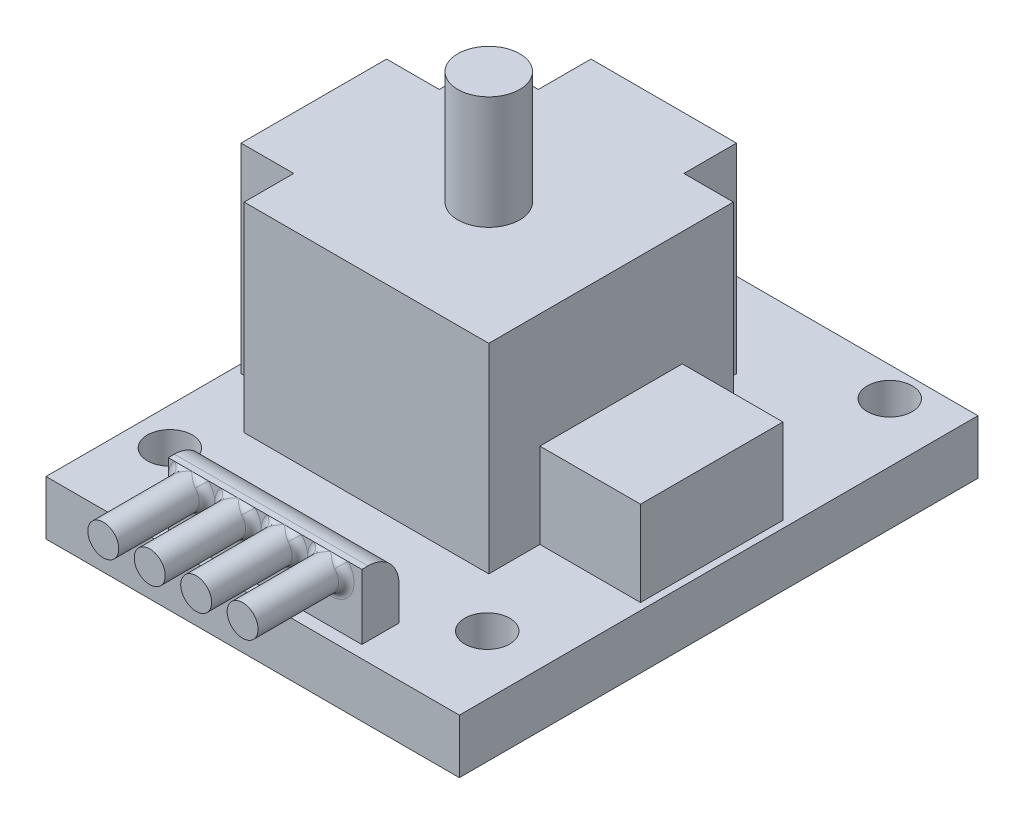
SolidWorks part; units mm, degrees
ref_plane "Спереди" through (0, 0, 0) normal (0, 0, 1) x (1, 0, 0)
ref_plane "Сверху" through (0, 0, 0) normal (0, 1, 0) x (1, 0, 0)
ref_plane "Справа" through (0, 0, 0) normal (1, 0, 0) x (0, 0, -1)
sketch "Sketch1" plane through (0, 0, 0) normal (0, 1, 0) x (1, 0, 0)
  line L1 (13.35, -16.75) -> (-13.35, -16.75)
  line L2 (13.35, -16.75) -> (13.35, 16.75)
  line L3 (13.35, 16.75) -> (-13.35, 16.75)
  line L4 (-13.35, -16.75) -> (-13.35, 16.75)
  line L5 (13.35, -16.75) -> (-13.35, 16.75) construction
  line L6 (13.35, 16.75) -> (-13.35, -16.75) construction
  point P0 (0, 0)
  dimension "D1" = 26.7
  dimension "D2" = 33.5
extrude "Boss-Extrude1" add sketch "Sketch1" along normal blind 3.5
sketch "Sketch2" plane through (0, 3.5, 0) normal (0, 1, 0) x (1, 0, 0)
  line L0 (13.35, 0) -> (-13.35, 0) construction
  line L1 (6.4, -7.9) -> (-9.4, -7.9)
  line L2 (6.4, -7.9) -> (6.4, 7.9)
  line L3 (6.4, 7.9) -> (-9.4, 7.9)
  line L4 (-9.4, -7.9) -> (-9.4, 7.9)
  line L5 (6.4, -7.9) -> (-9.4, 7.9) construction
  line L6 (6.4, 7.9) -> (-9.4, -7.9) construction
  line L7 (13.35, -16.75) -> (13.35, 16.75) construction
  line L8 (-13.35, 16.75) -> (-13.35, -16.75) construction
  point P0 (-1.5, 0)
  dimension "D1" = 15.8
  dimension "D2" = 1.5
extrude "Boss-Extrude2" add sketch "Sketch2" along normal blind 12.9
sketch "Sketch3" plane through (0, 16.4, 0) normal (0, 1, 0) x (1, 0, 0)
  circle A0 centre (0, 0) radius 1.9
  dimension "D1" = 3.8
extrude "Boss-Extrude3" add sketch "Sketch3" along normal blind 6.9
sketch "Sketch4" plane through (-9.4, 0, 0) normal (-1, 0, 0) x (0, 0, 1)
  line L0 (0, 16.4) -> (0, 3.5) construction
  line L1 (-7.9, 16.4) -> (7.9, 16.4) construction
  line L2 (-7.9, 3.5) -> (7.9, 3.5) construction
  line L4 (4.7, 3.5) -> (-4.7, 3.5)
  line L5 (4.7, 3.5) -> (4.7, 16.4)
  line L6 (4.7, 16.4) -> (-4.7, 16.4)
  line L7 (-4.7, 3.5) -> (-4.7, 16.4)
  line L8 (4.7, 3.5) -> (-4.7, 16.4) construction
  line L9 (4.7, 16.4) -> (-4.7, 3.5) construction
  point P6 (0, 9.95)
  dimension "D1" = 9.4
extrude "Boss-Extrude4" add sketch "Sketch4" along normal blind 3.4
sketch "Sketch5" plane through (0, 0, -7.9) normal (0, 0, -1) x (-1, 0, 0)
  line L0 (1.5, 16.4) -> (1.5, 3.5) construction
  line L1 (-6.4, 16.4) -> (9.4, 16.4) construction
  line L2 (-6.4, 3.5) -> (9.4, 3.5) construction
  line L4 (-3.2, 3.5) -> (6.2, 3.5)
  line L5 (-3.2, 3.5) -> (-3.2, 16.4)
  line L6 (-3.2, 16.4) -> (6.2, 16.4)
  line L7 (6.2, 3.5) -> (6.2, 16.4)
  line L8 (-3.2, 3.5) -> (6.2, 16.4) construction
  line L9 (-3.2, 16.4) -> (6.2, 3.5) construction
  point P6 (1.5, 9.95)
  dimension "D1" = 9.4
extrude "Boss-Extrude5" add sketch "Sketch5" along normal blind 3.4
sketch "Sketch6" plane through (6.4, 0, 0) normal (1, 0, 0) x (0, 0, -1)
  line L0 (0, 16.4) -> (0, 3.5) construction
  line L1 (-7.9, 16.4) -> (7.9, 16.4) construction
  line L2 (-7.9, 3.5) -> (7.9, 3.5) construction
  line L4 (-4.6, 9) -> (4.6, 9)
  line L5 (-4.6, 9) -> (-4.6, 3.5)
  line L6 (-4.6, 3.5) -> (4.6, 3.5)
  line L7 (4.6, 9) -> (4.6, 3.5)
  line L8 (-4.6, 9) -> (4.6, 3.5) construction
  line L9 (-4.6, 3.5) -> (4.6, 9) construction
  point P6 (0, 6.25)
  dimension "D1" = 9.2
  dimension "D2" = 5.5
extrude "Boss-Extrude6" add sketch "Sketch6" along normal blind 6.5
sketch "Sketch8" plane through (0, 16.4, 0) normal (0, 1, 0) x (1, 0, 0)
  line L0 (6.4, 7.9) -> (-9.4, -7.9) construction
  circle A0 centre (-1.5, 0) radius 12.75
  point P8 (-1.5, 0)
  dimension "D1" = 25.5
extrude "Boss-Extrude7" add sketch "Sketch8" along normal blind 8
fillet "Fillet1" radius 8 1 edges at (-1.5, 24.4, 12.75)
sketch "Sketch9" plane through (0, 24.4, 0) normal (0, 1, 0) x (1, 0, 0)
  circle A0 centre (-1.5, 0) radius 4.75
extrude "Boss-Extrude8" add sketch "Sketch9" along normal blind 5.5
sketch "Sketch10" plane through (0, 29.9, 0) normal (0, 1, 0) x (1, 0, 0)
  circle A0 centre (-1.5, 0) radius 10
  dimension "D1" = 20
extrude "Boss-Extrude9" add sketch "Sketch10" along normal blind 4.4
fillet "Fillet2" radius 4 1 edges at (-1.5, 34.3, 10)
sketch "Sketch11" plane through (0, 3.5, 0) normal (0, 1, 0) x (1, 0, 0)
  line L0 (-13.35, -14.75) -> (13.35, -14.75) construction
  line L1 (-13.35, 16.75) -> (-13.35, -16.75) construction
  line L2 (13.35, -16.75) -> (13.35, 16.75) construction
  line L3 (-13.35, -16.75) -> (13.35, -16.75) construction
  line L5 (6.25, -15.95) -> (-6.25, -15.95)
  line L6 (6.25, -15.95) -> (6.25, -13.55)
  line L7 (6.25, -13.55) -> (-6.25, -13.55)
  line L8 (-6.25, -15.95) -> (-6.25, -13.55)
  line L9 (6.25, -15.95) -> (-6.25, -13.55) construction
  line L10 (6.25, -13.55) -> (-6.25, -15.95) construction
  point P8 (0, -14.75)
  dimension "D1" = 2
  dimension "D2" = 2.4
  dimension "D3" = 12.5
extrude "Boss-Extrude10" add sketch "Sketch11" along normal blind 4.2
sketch "Sketch12" plane through (0, 0, 15.95) normal (0, 0, 1) x (1, 0, 0)
  line L0 (-6.25, 6.7) -> (6.25, 6.7) construction
  line L1 (-6.25, 7.7) -> (-6.25, 3.5) construction
  line L2 (6.25, 7.7) -> (6.25, 3.5) construction
  circle A0 centre (-4.75, 6.7) radius 1
  circle A1 centre (-1.75, 6.7) radius 1
  circle A2 centre (1.25, 6.7) radius 1
  circle A3 centre (4.25, 6.7) radius 1
  dimension "D1" = 1
  dimension "D2" = 3
  dimension "D3" = 3
  dimension "D4" = 3
  dimension "D5" = 1.5
extrude "Boss-Extrude11" add sketch "Sketch12" along normal blind 5.7
fillet "Fillet3" radius 2 1 edges at (0, 7.7, 13.55)
fillet "Fillet4" radius 0.5 4 edges at (5.25, 6.7, 15.95) (2.25, 6.7, 15.95) (-0.75, 6.7, 15.95) (-3.75, 6.7, 15.95)
sketch "Sketch13" plane through (0, 0, 0) normal (0, -1, 0) x (1, 0, 0)
  line L0 (9.55, -14.85) -> (-10.95, -14.85) construction
  line L1 (-10.95, -14.85) -> (-10.95, 11.15) construction
  line L2 (-10.95, 11.15) -> (9.55, 11.15) construction
  line L3 (9.55, 11.15) -> (9.55, -14.85) construction
  line L4 (13.35, -16.75) -> (-13.35, -16.75) construction
  line L5 (-13.35, -16.75) -> (-13.35, 16.75) construction
  circle A0 centre (9.55, -14.85) radius 1.45
  circle A1 centre (-10.95, -14.85) radius 1.45
  circle A2 centre (-10.95, 11.15) radius 1.45
  circle A3 centre (9.55, 11.15) radius 1.45
  dimension "D1" = 2.9
  dimension "D2" = 20.5
  dimension "D3" = 26
  dimension "D4" = 1.9
  dimension "D5" = 2.4
extrude "Cut-Extrude1" cut sketch "Sketch13" against normal up to next
sketch "Sketch14" plane through (0, 34.3, 0) normal (0, 1, 0) x (1, 0, 0)
  line L0 (-1.5, 6) -> (-1.5, -6) construction
  circle A0 centre (-1.5, 0) radius 6 construction
  circle A1 centre (-1.5, 0) radius 2
  dimension "D1" = 4
extrude "Cut-Extrude2" cut sketch "Sketch14" against normal up to surface (17.9 mm away) flip side to cut up to face at (-4.7, 16.4, -3.2)
sketch "Sketch15" plane through (0, 34.3, 0) normal (0, 1, 0) x (1, 0, 0)
  line L0 (0.5, 0) -> (-3.5, 0) construction
  circle A0 centre (-1.5, 0) radius 2 construction
  circle A1 centre (-1.5, 0) radius 2
extrude "Cut-Extrude3" cut sketch "Sketch15" against normal offset from surface (10.6 mm away) 7.3 up to face at (-4.7, 16.4, -3.2)
